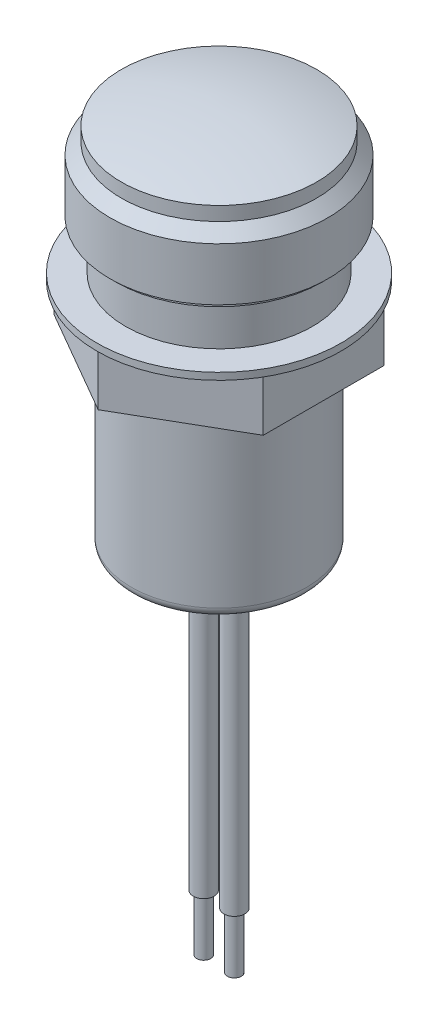
SolidWorks part; units mm, degrees
ref_plane "Front Plane" through (0, 0, 0) normal (0, 0, 1) x (1, 0, 0)
ref_plane "Top Plane" through (0, 0, 0) normal (0, 1, 0) x (1, 0, 0)
ref_plane "Right Plane" through (0, 0, 0) normal (1, 0, 0) x (0, 0, -1)
sketch "Sketch1" plane through (0, 0, 0) normal (0, 0, 1) x (1, 0, 0)
  line L0 (0, 0) -> (0, 35.56) construction
  line L1 (0, 35.56) -> (8.89, 35.56)
  line L2 (8.89, 35.56) -> (8.89, 34.29)
  line L3 (8.89, 34.29) -> (9.9187, 33.2613)
  line L4 (9.9187, 33.2613) -> (9.9187, 28.448)
  line L5 (9.9187, 28.448) -> (9.4043, 28.448)
  line L6 (9.4043, 28.448) -> (9.4044, 27.94)
  line L7 (9.4044, 27.94) -> (8.5, 27.94)
  line L8 (8.5, 27.94) -> (8.5, 23.9776)
  line L9 (8.5, 23.9776) -> (11.1125, 23.9776)
  line L10 (11.1125, 23.9776) -> (11.1125, 18.669)
  line L11 (0, 0) -> (0, 35.56)
  line L13 (11.1125, 18.669) -> (7.992, 18.669)
  line L14 (7.992, 18.669) -> (7.992, 2.286)
  line L15 (7.992, 2.286) -> (3.81, 2.286)
  line L16 (3.81, 2.286) -> (3.81, 0)
  line L17 (3.81, 0) -> (0, 0)
  line L18 (9.4044, 33.7756) -> (9.4043, 28.448) construction
  point P13 (3.6928, 2.2658)
  point P14 (12.5566, 18.669)
  point P17 (12.5566, 23.9776)
  point P21 (12.6794, 18.669)
  dimension "D1" = 35.56
  dimension "D2" = 3.9624
  dimension "D3" = 9.271
  dimension "D4" = 7.62
  dimension "D5" = 17
  dimension "D6" = 17.78
  dimension "D7" = 19.8374
  dimension "D8" = 0.508
  dimension "D9" = 45
  dimension "D10" = 1.27
  dimension "D11" = 22.225
  dimension "D12" = 0.508
  dimension "D13" = 2.286
  dimension "D14" = 7.62
revolve "Revolve1" add sketch "Sketch1" angle 360 about L11
dome "Dome1" faces to dome 1 distance 1.27 reverse direction no elliptical dome no face at (0, 35.56, -8.89) parameters "D1"=1.27
sketch "Sketch2" plane through (0, 18.669, 0) normal (0, -1, 0) x (1, 0, 0)
  line L1 (0, 10.9985) -> (-9.525, 5.4993)
  line L2 (-9.525, 5.4993) -> (-9.525, -5.4993)
  line L3 (-9.525, -5.4993) -> (0, -10.9985)
  line L4 (0, -10.9985) -> (9.525, -5.4993)
  line L5 (9.525, -5.4993) -> (9.525, 5.4993)
  line L6 (9.525, 5.4993) -> (0, 10.9985)
  circle A0 centre (0, 0) radius 9.525 construction
  dimension "D1" = 19.05
extrude "Cut-Extrude1" cut sketch "Sketch2" against normal offset from surface (4.6736 mm away) 0.635 flip side to cut up to face at (0, 23.9776, -8.5)
sketch "Sketch3" plane through (0, 0, 0) normal (0, -1, 0) x (1, 0, 0)
  line L0 (-1.397, 0) -> (1.397, 0) construction
  circle A0 centre (-1.397, 0) radius 0.9525
  circle A1 centre (1.397, 0) radius 0.9525
  dimension "D1" = 1.905
  dimension "D2" = 2.794
extrude "Boss-Extrude1" add sketch "Sketch3" along normal blind 25.4
sketch "Sketch4" plane through (0, -25.4, 0) normal (0, -1, 0) x (1, 0, 0)
  circle A0 centre (1.397, 0) radius 0.635
  circle A1 centre (-1.397, 0) radius 0.635
  dimension "D1" = 1.27
extrude "Boss-Extrude2" add sketch "Sketch4" along normal blind 5.08
fillet "Fillet1" radius 0.889 1 edges at (0, 2.286, -7.992)
fillet "Fillet2" radius 0.381 2 edges at (0, 0, -3.81) (0, 2.286, -3.81)
